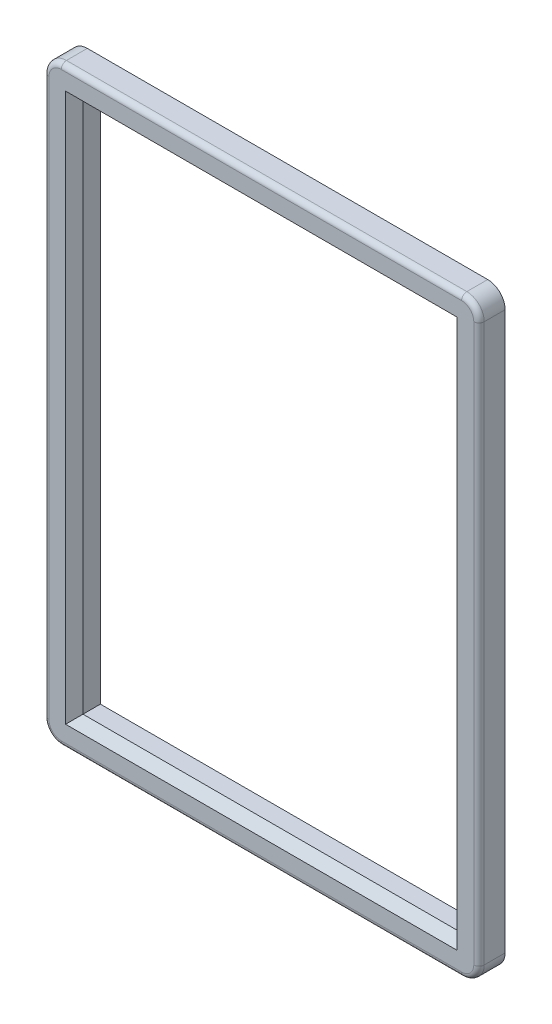
SolidWorks part; units mm, degrees
ref_plane "前视基准面" through (0, 0, 0) normal (0, 0, 1) x (1, 0, 0)
ref_plane "上视基准面" through (0, 0, 0) normal (0, 1, 0) x (1, 0, 0)
ref_plane "右视基准面" through (0, 0, 0) normal (1, 0, 0) x (0, 0, -1)
other "Configuration Table"
sketch "草图1" plane through (0, 0, 0) normal (0, 0, 1) x (1, 0, 0)
  line L1 (-25, -34) -> (25, -34)
  line L2 (-25, -34) -> (-25, 34)
  line L3 (-25, 34) -> (25, 34)
  line L4 (25, -34) -> (25, 34)
  line L5 (-25, -34) -> (25, 34) construction
  line L6 (-25, 34) -> (25, -34) construction
  line L7 (-21.5, -30.5) -> (21.5, -30.5)
  line L8 (-21.5, -30.5) -> (-21.5, 30.5)
  line L9 (-21.5, 30.5) -> (21.5, 30.5)
  line L10 (21.5, -30.5) -> (21.5, 30.5)
  line L11 (-21.5, -30.5) -> (21.5, 30.5) construction
  line L12 (-21.5, 30.5) -> (21.5, -30.5) construction
  line L13 (-23, -32) -> (23, -32) construction
  line L14 (-23, -32) -> (-23, 32) construction
  line L15 (-23, 32) -> (23, 32) construction
  line L16 (23, -32) -> (23, 32) construction
  line L17 (-23, -32) -> (23, 32) construction
  line L18 (-23, 32) -> (23, -32) construction
  circle A0 centre (-23, 32) radius 0.5
  circle A1 centre (23, 32) radius 0.5
  circle A2 centre (23, -32) radius 0.5
  circle A3 centre (-23, -32) radius 0.5
  point P0 (0, 0)
  point P6 (0, 0)
  point P12 (0, 0)
extrude "凸台-拉伸1" add sketch "草图1" along normal blind 3 contours L1 L4 L3 L2 A3 A2 A1 A0 L10 L7 L8 L9 | A2 | A3 | A0 | A1 region at (-24.156, 0, 0) region at (-23, 32, 0) region at (23, 32, 0) region at (23, -32, 0) region at (-23, -32, 0)
fillet "圆角1" radius 2 4 edges at (-25, -34, 1.5) (25, -34, 1.5) (25, 34, 1.5) (-25, 34, 1.5)
extrude "切除-拉伸1" cut sketch "草图1<5>" along normal blind 2 contours A1 | A0 | A3 | A2 region at (-23, 32, 0) region at (23, 32, 0)
sketch "草图1<5>" plane through (0, 0, 0) normal (0, 0, 1) x (1, 0, 0) same geometry as "草图1"
fillet "圆角2" radius 0.6 8 edges at (24.4142, -33.4142, 3) (0, -34, 3) (-24.4142, -33.4142, 3) (-25, 0, 3) (-24.4142, 33.4142, 3) (0, 34, 3) (24.4142, 33.4142, 3) (25, 0, 3)
chamfer "倒角1" distance 1 angle 45 4 edges at (21.5, 0, 3) (0, 30.5, 3) (0, -30.5, 3) (-21.5, 0, 3)
